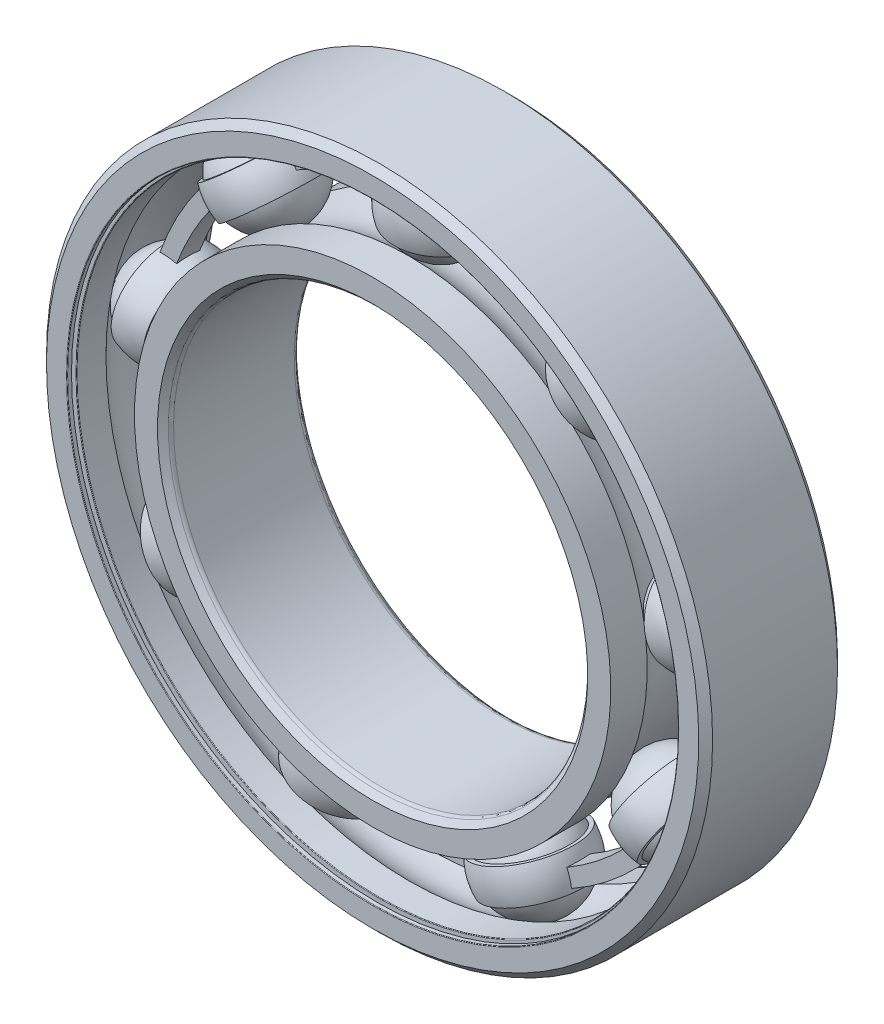
SolidWorks part; units mm, degrees
ref_plane "Front Plane" through (0, 0, 0) normal (0, 0, 1) x (1, 0, 0)
ref_plane "Top Plane" through (0, 0, 0) normal (0, 1, 0) x (1, 0, 0)
ref_plane "Right Plane" through (0, 0, 0) normal (1, 0, 0) x (0, 0, -1)
sketch "Sketch1" plane through (0, 0, 0) normal (0, 0, 1) x (1, 0, 0)
  line L0 (-12, 0) -> (12, 0) construction
  line L1 (-7.5, 0) -> (7.5, 0) construction
  circle A0 centre (0, 0) radius 7.5 construction
  circle A1 centre (0, 0) radius 12 construction
  point P3 (0, 0)
  point P6 (0, 0)
  point P7 (0, -7.5)
  point P11 (0, -12)
  point P12 (0, 7.5)
  point P13 (0, 12)
  dimension "OD" = 24
  dimension "ID" = 15
sketch "Sketch2" plane through (0, 0, 0) normal (1, 0, 0) x (0, 0, -1)
  line L0 (-2.5, 12) -> (2.5, 12) construction
  line L1 (0, 12) -> (0, -12) construction
  line L2 (2.25, 12) -> (-2.25, 12)
  line L3 (-2.25, 12) -> (-2.5, 11.75)
  line L4 (-2.5, 11.75) -> (-2.5, 10.9192)
  line L5 (-2.5, 10.9192) -> (-1.1875, 10.9192)
  line L6 (2.5, 10.9192) -> (1.1875, 10.9192)
  line L7 (2.5, 11.75) -> (2.5, 10.9192)
  line L8 (2.25, 12) -> (2.5, 11.75)
  line L9 (0, 12) -> (0, 9.75) construction
  line L10 (0, 9.75) -> (0, 7.5) construction
  line L11 (0, 12) -> (0, -12) construction
  line L12 (-2.5, 0) -> (2.5, 0) construction
  line L13 (2.5, 7.5) -> (-2.5, 7.5) construction
  line L14 (0, 11.4165) -> (0, 8.0835) construction
  line L15 (-2.5, -7.5) -> (2.5, -7.5) construction
  line L16 (-2.5, -7.5) -> (-2.5, 7.5) construction
  line L17 (2.5, 12) -> (2.5, -12) construction
  arc A0 (-1.1875, 10.9192) -> (1.1875, 10.9192) centre (0, 9.75) cw
  circle A1 centre (0, 9.75) radius 1.6665 construction
  point P14 (0, 7.5)
  point P17 (0, 0)
  point P21 (0, 12)
  point P29 (0, 7.5)
  point P30 (0, -7.5)
  point P35 (0, 11.4165)
  dimension "Approx. Ball Dia." = 3.333
  dimension "Width" = 5
  dimension "D1" = 45
  dimension "D2" = 0.25
  dimension "D3" = 2.375
  dimension "D4" = 1.1692
  dimension "For Shaft Diameter" = 15
  dimension "For Housing ID" = 24
sketch "Sketch3" plane through (0, 0, 0) normal (1, 0, 0) x (0, 0, -1)
  line L0 (2.25, 12) -> (2.5, 11.75) construction
  line L1 (2.5, 11.75) -> (2.5, 10.9192) construction
  line L2 (2.5, 10.9192) -> (1.1875, 10.9192) construction
  line L3 (-2.5, 10.9192) -> (-1.1875, 10.9192) construction
  line L4 (-2.5, 11.75) -> (-2.5, 10.9192) construction
  line L5 (-2.25, 12) -> (-2.5, 11.75) construction
  line L6 (2.25, 12) -> (-2.25, 12) construction
  line L7 (2.25, 12) -> (2.5, 11.75)
  line L8 (2.5, 11.75) -> (2.5, 10.9192)
  line L9 (2.5, 10.9192) -> (1.1875, 10.9192)
  line L10 (-2.5, 10.9192) -> (-1.1875, 10.9192)
  line L11 (-2.5, 11.75) -> (-2.5, 10.9192)
  line L12 (-2.25, 12) -> (-2.5, 11.75)
  line L13 (2.25, 12) -> (-2.25, 12)
  arc A0 (1.1875, 10.9192) -> (-1.1875, 10.9192) centre (0, 9.75) ccw construction
  arc A1 (1.1875, 10.9192) -> (-1.1875, 10.9192) centre (0, 9.75) ccw
revolve "Revolve1" add sketch "Sketch3" angle 360 about L12
sketch "Sketch8" plane through (0, 0, 0) normal (1, 0, 0) x (0, 0, -1)
  line L0 (-2.5, 10.9192) -> (-1.1875, 10.9192) construction
  line L1 (-2.34, 10.9192) -> (-2.25, 10.9192)
  line L2 (-2.34, 10.9192) -> (-2.34, 11.2795) construction
  line L3 (-2.34, 11.2795) -> (-2.25, 11.2795)
  line L4 (-2.25, 10.9192) -> (-2.25, 11.2795)
  line L5 (2.5, 10.9192) -> (1.1875, 10.9192) construction
  line L6 (2.25, 10.9192) -> (2.34, 10.9192)
  line L7 (2.25, 10.9192) -> (2.25, 11.2795)
  line L8 (2.25, 11.2795) -> (2.34, 11.2795)
  line L9 (2.34, 10.9192) -> (2.34, 11.2795) construction
  line L10 (-2.25, 11.2795) -> (2.25, 11.2795) construction
  line L11 (0, 12) -> (0, -12) construction
  line L12 (-2.34, 11.2795) -> (-2.34, 11.6397) construction
  line L13 (-2.34, 11.6397) -> (-2.34, 12) construction
  line L14 (-2.5, 12) -> (2.5, 12) construction
  line L15 (-2.34, 10.9192) -> (-2.5, 10.9192)
  line L16 (-2.5, 10.9192) -> (-2.5, 11.0092)
  line L17 (-2.5, 11.75) -> (-2.5, 10.9192) construction
  line L18 (-2.5, 11.0092) -> (-2.34, 11.0092)
  line L19 (-2.34, 11.0092) -> (-2.34, 11.2795)
  line L20 (2.34, 10.9192) -> (2.5, 10.9192)
  line L21 (2.5, 10.9192) -> (2.5, 11.0092)
  line L22 (2.5, 11.75) -> (2.5, 10.9192) construction
  line L23 (2.5, 11.0092) -> (2.34, 11.0092)
  line L24 (2.34, 11.0092) -> (2.34, 11.2795)
  point P12 (0, 11.2795)
  dimension "D2" = 0.09
revolve "Cut-Revolve1" cut sketch "Sketch8" angle 360 about L12
sketch "Sketch4" plane through (0, 0, 0) normal (1, 0, 0) x (0, 0, -1)
  line L0 (0, 12) -> (0, -12) construction
  line L1 (0, 12) -> (0, -12) construction
  line L2 (-2.25, 7.5) -> (-2.5, 7.75)
  line L3 (-2.5, 7.75) -> (-2.5, 8.5808)
  line L5 (-2.5, 8.5808) -> (-1.1875, 8.5808)
  line L6 (-2.25, 7.5) -> (2.25, 7.5)
  line L8 (2.25, 7.5) -> (2.5, 7.75)
  line L10 (2.5, 7.75) -> (2.5, 8.5808)
  line L11 (2.5, 8.5808) -> (1.1875, 8.5808)
  line L12 (-2.5, 11.75) -> (-2.5, 10.9192) construction
  line L13 (2.25, 12) -> (2.5, 11.75) construction
  line L15 (2.5, -11.75) -> (2.5, 11.75) construction
  line L16 (2.25, 12) -> (2.25, -12) construction
  arc A1 (1.1875, 8.5808) -> (-1.1875, 8.5808) centre (0, 9.75) cw
  circle A2 centre (0, 9.75) radius 1.6665 construction
  point P1 (0, 7.5)
revolve "Revolve2" add sketch "Sketch4" angle 360 about L12
sketch "Sketch5" plane through (0, 0, 0) normal (1, 0, 0) x (0, 0, -1)
  line L0 (-1.6665, 9.75) -> (1.6665, 9.75)
  arc A2 (-1.6665, 9.75) -> (1.6665, 9.75) centre (0, 9.75) cw
  arc A3 (1.1875, 10.9192) -> (-1.1875, 10.9192) centre (0, 9.75) ccw construction
revolve "Revolve3" add sketch "Sketch5" angle 360 about L0
sketch "Sketch6" plane through (0, 0, 0) normal (1, 0, 0) x (0, 0, -1)
  line L0 (-1.1875, 10.9192) -> (-1.1875, 10.3346) construction
  line L1 (-1.1875, 10.3346) -> (-1.1875, 9.75) construction
  line L2 (-1.1875, 9.75) -> (-1.1875, 9.1654) construction
  line L3 (-1.1875, 9.1654) -> (-1.1875, 8.5808) construction
  line L4 (-2.5, 10.3346) -> (-2.3434, 10.3346) construction
  line L5 (-1.1875, 10.3346) -> (-1.1875, 9.1654) construction
  line L7 (-2.3434, 10.3346) -> (-2.1869, 10.3346) construction
  line L8 (-2.1869, 10.3346) -> (-2.0303, 10.3346) construction
  line L10 (0, 12) -> (0, -12) construction
  line L11 (0, 12) -> (0, -12) construction
  line L12 (-2.5, 10.9192) -> (-2.5, 10.3346) construction
  line L13 (-1.7172, 10.3346) -> (-1.5606, 10.3346) construction
  line L14 (-2.5, 11.75) -> (-2.5, -11.75) construction
  line L15 (-2.5, 10.3346) -> (-2.5, 9.75) construction
  line L16 (-2.5, 9.75) -> (-2.5, 9.1654) construction
  line L17 (-2.5, 9.1654) -> (-2.5, 8.5808) construction
  line L18 (-2.0303, 10.3346) -> (-1.8737, 10.3346) construction
  line L19 (-1.8737, 10.3346) -> (-1.7172, 10.3346) construction
  line L20 (-1.5606, 10.3346) -> (-1.7172, 10.3346)
  line L21 (-2.5, 9.1654) -> (-2.3434, 9.1654) construction
  line L22 (-2.3434, 9.1654) -> (-2.1869, 9.1654) construction
  line L23 (-2.1869, 9.1654) -> (-2.0303, 9.1654) construction
  line L24 (-2.0303, 9.1654) -> (-1.8737, 9.1654) construction
  line L25 (-1.8737, 9.1654) -> (-1.7172, 9.1654) construction
  line L26 (-1.7172, 9.1654) -> (-1.5606, 9.1654) construction
  line L27 (-1.5606, 9.1654) -> (-1.7172, 9.1654)
  line L28 (-1.8737, 10.3346) -> (-1.8737, 9.1654) construction
  line L30 (-1.7955, 10.3346) -> (-1.7955, 9.1654) construction
  circle A0 centre (0, 9.75) radius 1.6665 construction
  arc A2 (-1.7172, 9.1654) -> (-1.7172, 10.3346) centre (0.4266, 9.75) cw
  arc A3 (-1.5606, 10.3346) -> (-1.5606, 9.1654) centre (0, 9.75) ccw
revolve "Revolve4" add sketch "Sketch6" angle 360 about L11
sketch "Sketch7" plane through (0, 0, 0) normal (0, 0, 1) x (1, 0, 0)
  line L0 (-1.6665, 9.75) -> (1.6665, 9.75) construction
  line L1 (0, 8.0835) -> (0, 11.4165) construction
  line L2 (0, 0) -> (3.3347, 9.162) construction
  line L8 (0, 12) -> (0, -12) construction
  line L9 (6.2672, 7.4689) -> (6.643, 7.9168)
  line L10 (0, 12) -> (0, -12) construction
  line L11 (0, 10.3346) -> (0, 9.75)
  arc A1 (6.2672, 7.4689) -> (0, 9.75) centre (0, 0) ccw
  arc A2 (6.643, 7.9168) -> (0, 10.3346) centre (0, 0) ccw
  dimension "D1" = 40
  dimension "D2" = 3.333
extrude "Boss-Extrude1" add sketch "Sketch7" along normal mid plane 0.8333
pattern_circular "CirPattern1" count 9 over 360 about axis through (0, 0, 2.5) along (0, 0, -1) of bodies 104 134
pattern_circular "CirPattern2" count 9 over 360 about axis through (0, 0, 2.5) along (0, 0, -1) of "Revolve4", "Boss-Extrude1" reverse direction yes
fillet "Fillet1" radius 0.0225 4 edges at (0, -10.9192, -2.25) (0, -11.0092, -2.5) (0, -10.9192, 2.25) (0, -11.0092, 2.5)
fillet "Fillet2" radius 0.1875 2 edges at (0, -7.5, -2.25) (0, -7.5, 2.25)
ref_plane "Plane1" through (3.3347, 9.162, 0) normal (0.342, 0.9397, 0) x (0.9397, -0.342, 0)
sketch "Sketch9" plane through (3.3347, 9.162, 0) normal (0.342, 0.9397, 0) x (0.9397, -0.342, 0)
  line L0 (-1.7687, -0.4167) -> (-1.7687, -1.25)
  line L1 (-1.7687, -1.25) -> (-0.7672, -1.25)
  line L2 (-0.7672, -1.25) -> (0, -0.6062)
  line L3 (0, -0.6062) -> (0.7672, -1.25)
  line L4 (0.7672, -1.25) -> (1.7687, -1.25)
  line L5 (1.7687, -1.25) -> (1.7687, -0.4167)
  line L6 (1.7687, -0.4167) -> (-1.7687, -0.4167)
  line L7 (0, -0.4167) -> (0, 0) construction
  line L8 (-1.7687, -0.4167) -> (-1.7687, 0) construction
  dimension "D1" = 0.8333
  dimension "D2" = 0.4167
  dimension "D3" = 40
extrude "Boss-Extrude2" [suppressed] add sketch "Sketch9" along normal blind 1.4582 draft 15 and the other way blind 1.4582 draft 10 separate body draft outward yes other way draft outward yes
fillet "Fillet3" [suppressed] radius 0.25
mirror "Mirror1" [suppressed] about plane through (0, 0, 0) normal (0, 0, 1) of bodies 149
pattern_circular "CirPattern3" [suppressed] count 9 over 360 about axis through (0, 0, 2.5) along (0, 0, -1) of bodies 158 149
equation "\"D2@Sketch2\" = \"Width@Sketch2\" * .05"
equation "\"D3@Sketch2\"=\"Width@Sketch2\" * .475"
equation "\"D4@Sketch2\" =  (  (  ( \"OD@Sketch1\" - \"Width@Sketch2\" )  / 2 )  / 3.25 )  / 2.5"
equation "\"D1@Boss-Extrude1\" = \"Width@Sketch2\" / 6"
equation "\"D1@Sketch8\"=\"Width@Sketch2\"*.9"
equation "\"D2@Sketch8\"=\"D1@Sketch8\"*.02"
equation "\"D1@Fillet1\" = \"D2@Sketch8\" * .25"
equation "\"D1@Fillet2\" = \"D2@Sketch2\" * .75"
equation "\"Approx No of Balls@CirPattern1\" = ( pi * \"OD@Sketch1\" ) * .4 / \"Approx. Ball Dia.@Sketch2\""
equation "\"D1@Sketch7\" = 360 / \"Approx No of Balls@CirPattern1\""
equation "\"D1@CirPattern2\" = \"Approx No of Balls@CirPattern1\""
equation "\"D2@Sketch7\"=\"Approx. Ball Dia.@Sketch2\""
equation "\"D2@Sketch9\" = \"D1@Boss-Extrude1\" * .5"
equation "\"D1@Sketch9\"=\"D2@Sketch9\"*2"
equation "\"D1@Boss-Extrude2\"=\"Approx. Ball Dia.@Sketch2\"*.4375"
equation "\"D2@Boss-Extrude2\"=\"D1@Boss-Extrude2\""
equation "\"D1@CirPattern3\" = \"Approx No of Balls@CirPattern1\""
equation "\"D1@Fillet3\"=\"D1@Sketch9\" * .3"
